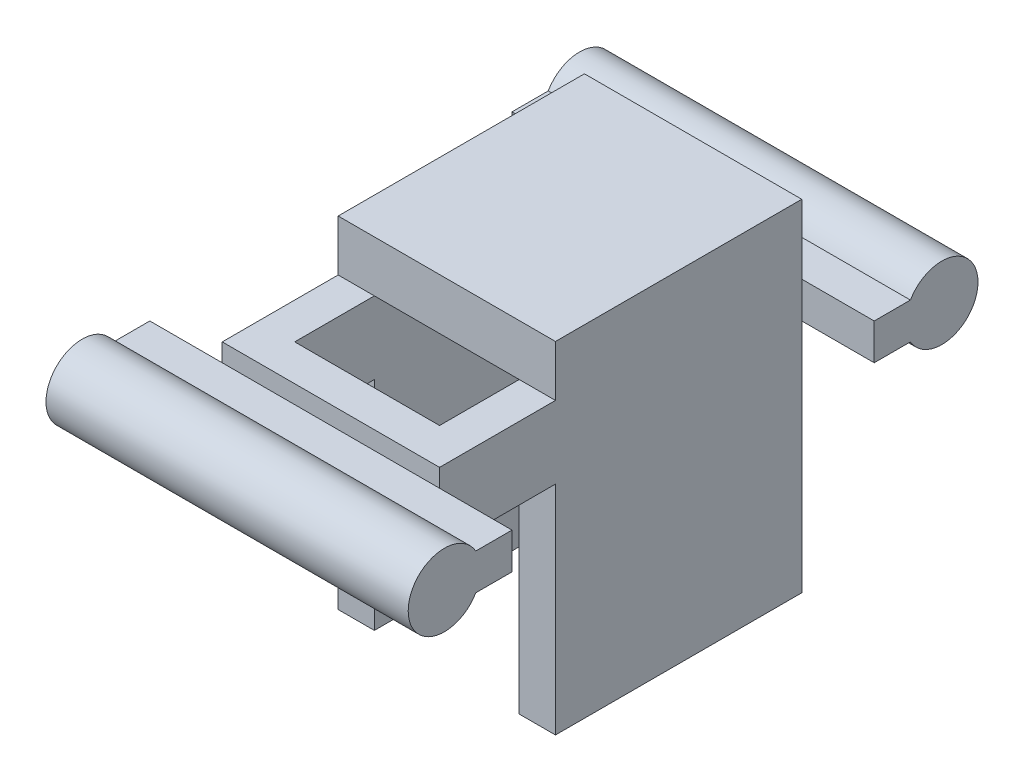
SolidWorks part; units mm, degrees
ref_plane "Plano frontal" through (0, 0, 0) normal (0, 0, 1) x (1, 0, 0)
ref_plane "Plano superior" through (0, 0, 0) normal (0, 1, 0) x (1, 0, 0)
ref_plane "Plano direito" through (0, 0, 0) normal (1, 0, 0) x (0, 0, -1)
sketch "Esboço2" plane through (0, 0, 0) normal (0, 0, 1) x (1, 0, 0)
  line L0 (0, 0) -> (0, 24.1482) construction
  line L1 (-10, 0) -> (10, 0) construction
  line L2 (10, 0) -> (10, -40)
  line L3 (10, 0) -> (-10, 0)
  line L4 (15, 0) -> (15, 7.05)
  line L5 (15, 7.05) -> (-15, 7.05)
  line L6 (0, 0) -> (0, 7.05) construction
  line L7 (10, -40) -> (15, -40)
  line L8 (15, -40) -> (15, 0)
  line L9 (-15, -40) -> (-15, 0)
  line L10 (-10, -40) -> (-15, -40)
  line L11 (-15, 0) -> (-15, 7.05)
  line L12 (-10, 0) -> (-10, -40)
  dimension "D1" = 15
  dimension "D2" = 7.05
  dimension "D3" = 40
  dimension "D4" = 5
extrude "Ressalto-extrusão2" add sketch "Esboço2" against normal blind 29
ref_plane "Plano1" through (-25, 0, 0) normal (-1, 0, 0) x (0, 0, 1)
sketch "Esboço3" plane through (0, 0, 0) normal (0, 0, 1) x (1, 0, 0)
  line L0 (15, -40) -> (15, 7.05) construction
  line L1 (10, 0) -> (15, 0)
  line L2 (10, 0) -> (10, -10)
  line L3 (10, -10) -> (15, -10)
  line L4 (15, 0) -> (15, -10)
  line L5 (0, -55) -> (0, 55) construction
  line L6 (-15, 0) -> (-15, -10)
  line L7 (-10, -10) -> (-15, -10)
  line L8 (-10, 0) -> (-10, -10)
  line L9 (-10, 0) -> (-15, 0)
  dimension "D1" = 10
extrude "Ressalto-extrusão3" add sketch "Esboço3" along normal blind 16
sketch "Esboço4" plane through (10, 0, 0) normal (-1, 0, 0) x (0, 0, 1)
  line L0 (16, -10) -> (0, -10) construction
  line L1 (16, 0) -> (11, 0)
  line L2 (16, 0) -> (16, -10)
  line L3 (16, -10) -> (11, -10)
  line L4 (11, 0) -> (11, -10)
  dimension "D1" = 5
extrude "Ressalto-extrusão4" add sketch "Esboço4" along normal up to surface (20 mm away) up to face at (-10, -14.2857, -3.7143)
sketch "Esboço5" plane through (0, 0, -29) normal (0, 0, -1) x (-1, 0, 0)
  line L1 (15, 7.05) -> (-15, 7.05)
  line L2 (15, 7.05) -> (15, -40)
  line L3 (15, -40) -> (-15, -40)
  line L4 (-15, 7.05) -> (-15, -40)
extrude "Ressalto-extrusão5" add sketch "Esboço5" along normal blind 5
sketch "Esboço6" plane through (-25, 0, 0) normal (-1, 0, 0) x (0, 0, 1)
  line L0 (16, -5) -> (25.3301, -5) construction
  line L1 (16, 0) -> (16, -10) construction
  line L2 (16, -2.5) -> (21, -2.5)
  line L3 (16, -7.5) -> (21, -7.5)
  line L4 (16, 0) -> (0, 0) construction
  line L5 (16, -10) -> (0, -10) construction
  line L6 (16, -2.5) -> (16, -7.5)
  line L7 (16, -5) -> (-34, -5) construction
  line L8 (-34, -40) -> (-34, 7.05) construction
  line L9 (-9, -5) -> (-9, 7.05) construction
  line L10 (-34, 7.05) -> (0, 7.05) construction
  line L11 (-34, -5) -> (-43.3301, -5) construction
  line L12 (-34, -2.5) -> (-34, -7.5)
  line L13 (-34, -7.5) -> (-39, -7.5)
  line L14 (-34, -2.5) -> (-39, -2.5)
  arc A0 (21, -7.5) -> (21, -2.5) centre (25.3301, -5) ccw
  arc A1 (-39, -7.5) -> (-39, -2.5) centre (-43.3301, -5) cw
  dimension "D3" = 10
  dimension "D1" = 2.5
  dimension "D2" = 2.5
  dimension "D4" = 5
extrude "Ressalto-extrusão6" add sketch "Esboço6" against normal blind 50
